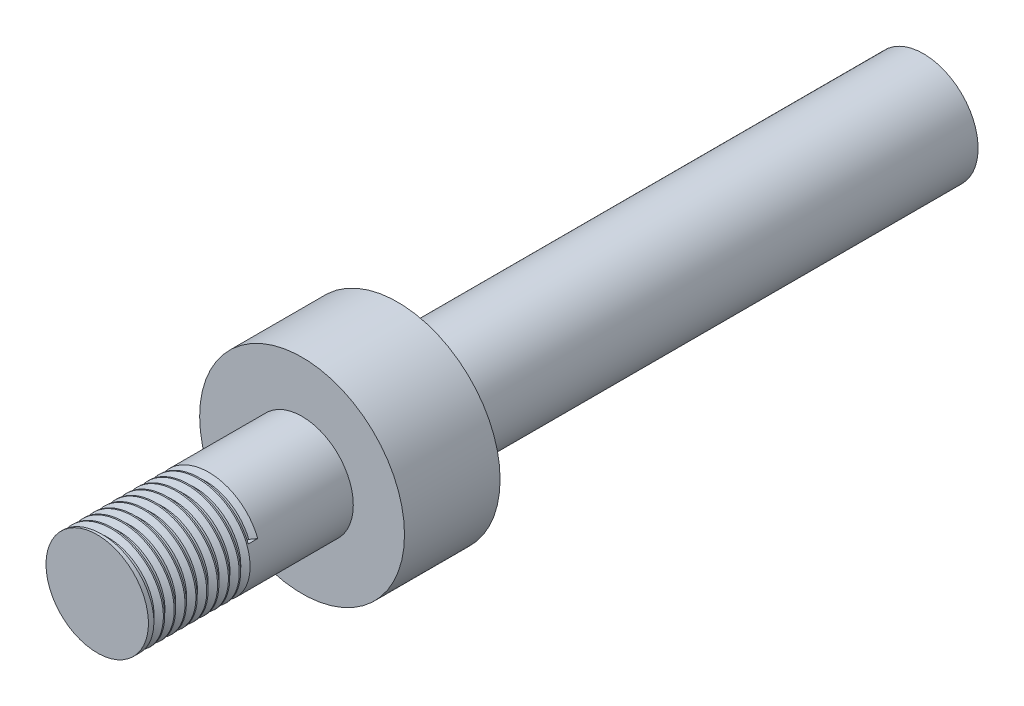
SolidWorks part; units mm, degrees
material "Plain Carbon Steel"
ref_plane "Front Plane" through (0, 0, 0) normal (0, 0, 1) x (1, 0, 0)
ref_plane "Top Plane" through (0, 0, 0) normal (0, 1, 0) x (1, 0, 0)
ref_plane "Right Plane" through (0, 0, 0) normal (1, 0, 0) x (0, 0, -1)
sketch "Sketch1" plane through (0, 0, 0) normal (0, 0, 1) x (1, 0, 0)
  circle A0 centre (0, 0) radius 1.6
  dimension "D1" = 3.2
extrude "Boss-Extrude1" add sketch "Sketch1" along normal blind 15.4
sketch "Sketch4" plane through (0, 0, 15.4) normal (0, 0, 1) x (1, 0, 0)
  circle A0 centre (0, 0) radius 3
  dimension "D1" = 6
extrude "Boss-Extrude2" add sketch "Sketch4" along normal blind 2.8
sketch "Sketch5" plane through (0, 0, 18.2) normal (0, 0, 1) x (1, 0, 0)
  circle A0 centre (0, 0) radius 1.5
  dimension "D1" = 3
extrude "Boss-Extrude3" add sketch "Sketch5" along normal blind 6
thread "Thread2" pitch 0.3175 method cut profile "Thread Profile2" start angle 0, offset 0, length 3, pitch 0.3175, diameter 3
ref_plane "Plane2" through (-1.5, 0, 24.2) normal (0, -1, 0) x (-1, 0, 0)
sketch "Thread Profile2" plane through (-1.5, 0, 24.2) normal (0, -1, 0) x (-1, 0, 0)
  line L0 (0, 0) -> (0, 0.3175) construction
  line L11 (0, 0) -> (0, 0.2778)
  line L12 (0, 0.2778) -> (-0.1719, 0.1786)
  line L13 (-0.1719, 0.1786) -> (-0.1719, 0.0992)
  line L15 (-0.1719, 0.0992) -> (0, 0)
  line L17 (-0.1719, 0.1389) -> (0, 0.1389) construction
  point P2 (0, 0)
  dimension "Pitch" = 0.3175
  dimension "Profile_Angle" = 60
  dimension "Profile_Land" = 0.0794
  dimension "Profile_Height" = 0.1719
